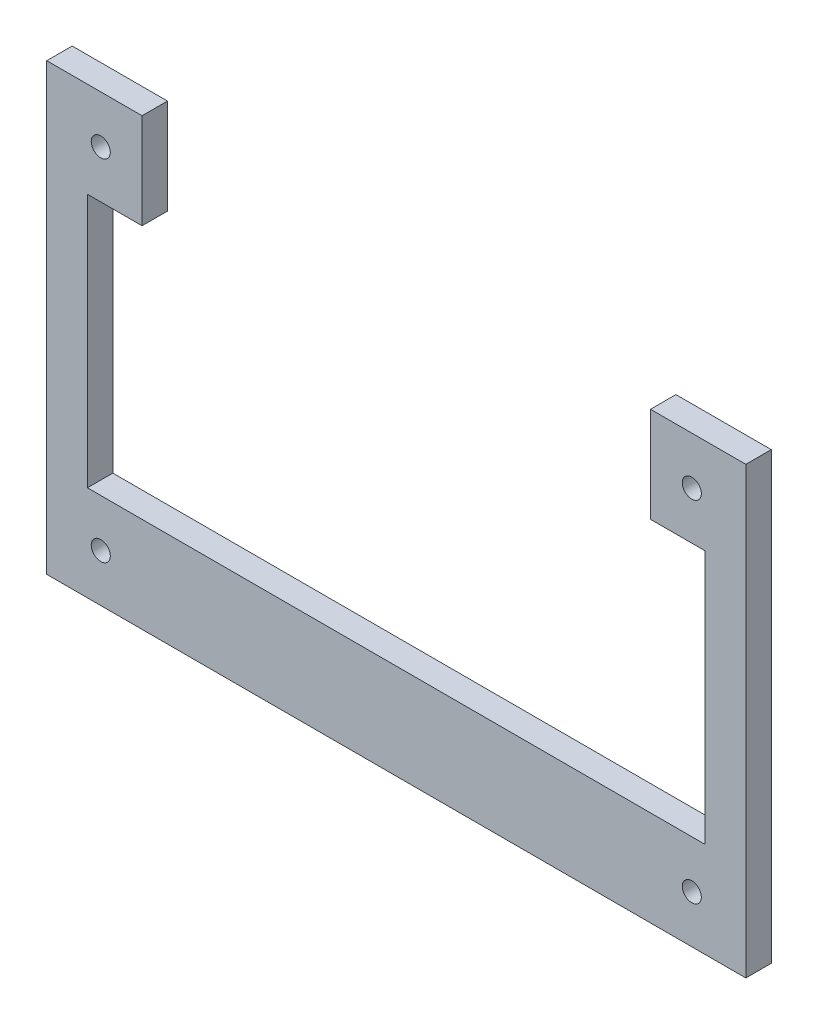
SolidWorks part; units mm, degrees
ref_plane "Front Plane" through (0, 0, 0) normal (0, 0, 1) x (1, 0, 0)
ref_plane "Top Plane" through (0, 0, 0) normal (0, 1, 0) x (1, 0, 0)
ref_plane "Right Plane" through (0, 0, 0) normal (1, 0, 0) x (0, 0, -1)
sketch "Sketch1" plane through (0, 0, 0) normal (0, 0, 1) x (1, 0, 0)
  line L1 (-55, -35) -> (55, -35)
  line L2 (-55, -35) -> (-55, 35)
  line L3 (-55, 35) -> (55, 35)
  line L4 (55, -35) -> (55, 35)
  line L5 (-55, -35) -> (55, 35) construction
  line L6 (-55, 35) -> (55, -35) construction
  point P0 (0, 0)
  dimension "D1" = 110
  dimension "D2" = 70
extrude "Plate" add sketch "Sketch1" along normal blind 4
sketch "Sketch2" plane through (0, 0, 0) normal (0, 0, -1) x (-1, 0, 0)
  line L1 (-48.6, -20) -> (48.6, -20)
  line L2 (-48.6, -20) -> (-48.6, 20)
  line L3 (-48.6, 20) -> (48.6, 20)
  line L4 (48.6, -20) -> (48.6, 20)
  line L5 (-48.6, -20) -> (48.6, 20) construction
  line L6 (-48.6, 20) -> (48.6, -20) construction
  point P0 (0, 0)
  dimension "D1" = 97.2
  dimension "D2" = 40
extrude "Screen hole" cut sketch "Sketch2" against normal through all
sketch "Sketch4" plane through (0, 0, 0) normal (0, 0, -1) x (-1, 0, 0)
  line L0 (48.6, -20) -> (48.6, 20) construction
  line L1 (-48.6, -20) -> (48.6, -20) construction
  line L2 (-48.6, 20) -> (-48.6, -20) construction
  line L3 (48.6, 20) -> (-48.6, 20) construction
  line L4 (48.6, -20) -> (48.6, 20)
  line L5 (-48.6, -20) -> (48.6, -20)
  line L6 (-48.6, 20) -> (-48.6, -20)
  line L7 (48.6, 20) -> (-48.6, 20)
  line L8 (-48.6, 20) -> (48.6, -20) construction
  line L10 (-46.5, -27.5) -> (46.5, -27.5)
  line L11 (-46.5, -27.5) -> (-46.5, 27.5)
  line L12 (-46.5, 27.5) -> (46.5, 27.5)
  line L13 (46.5, -27.5) -> (46.5, 27.5)
  line L14 (-46.5, -27.5) -> (46.5, 27.5) construction
  line L15 (-46.5, 27.5) -> (46.5, -27.5) construction
  point P3 (0, 0)
  dimension "D1" = 93
  dimension "D2" = 55
hole_wizard "Ø3.0mm Dowel Hole1" positions "3DSketch1" profile "Sketch5" hole size "Ø3.0" standard "ISO" end condition up to next
sketch3d "3DSketch1"
  point P0 (46.5, 27.5, 0)
  point P3 (-46.5, 27.5, 0)
  point P6 (-46.5, -27.5, 0)
  point P9 (46.5, -27.5, 0)
sketch "Sketch5" plane through (46.5, 27.5, 0) normal (1, 0, 0) x (0, 1, 0)
  line L0 (0, 0) -> (0, 4)
  line L1 (0, 4) -> (1.5, 4)
  line L2 (1.5, 4) -> (1.5, 0)
  line L5 (1.5, 0) -> (0, 0)
  line L11 (0, -6.35) -> (0, 107.95) construction
  dimension "Thru Hole Dia." = 3
  dimension "Thru Hole Depth" = 4
sketch "Sketch6" plane through (0, 0, 0) normal (0, 0, -1) x (-1, 0, 0)
  line L0 (48.6, 20) -> (-48.6, 20) construction
  line L1 (-40, 20) -> (40, 20)
  line L2 (-40, 20) -> (-40, 35)
  line L3 (-40, 35) -> (40, 35)
  line L4 (40, 20) -> (40, 35)
  line L5 (-55, 35) -> (55, 35) construction
  line L6 (-55, -35) -> (-55, 35) construction
  line L7 (55, 35) -> (55, -35) construction
  dimension "D1" = 15
  dimension "D2" = 15
extrude "Cut-Extrude1" cut sketch "Sketch6" against normal through all
